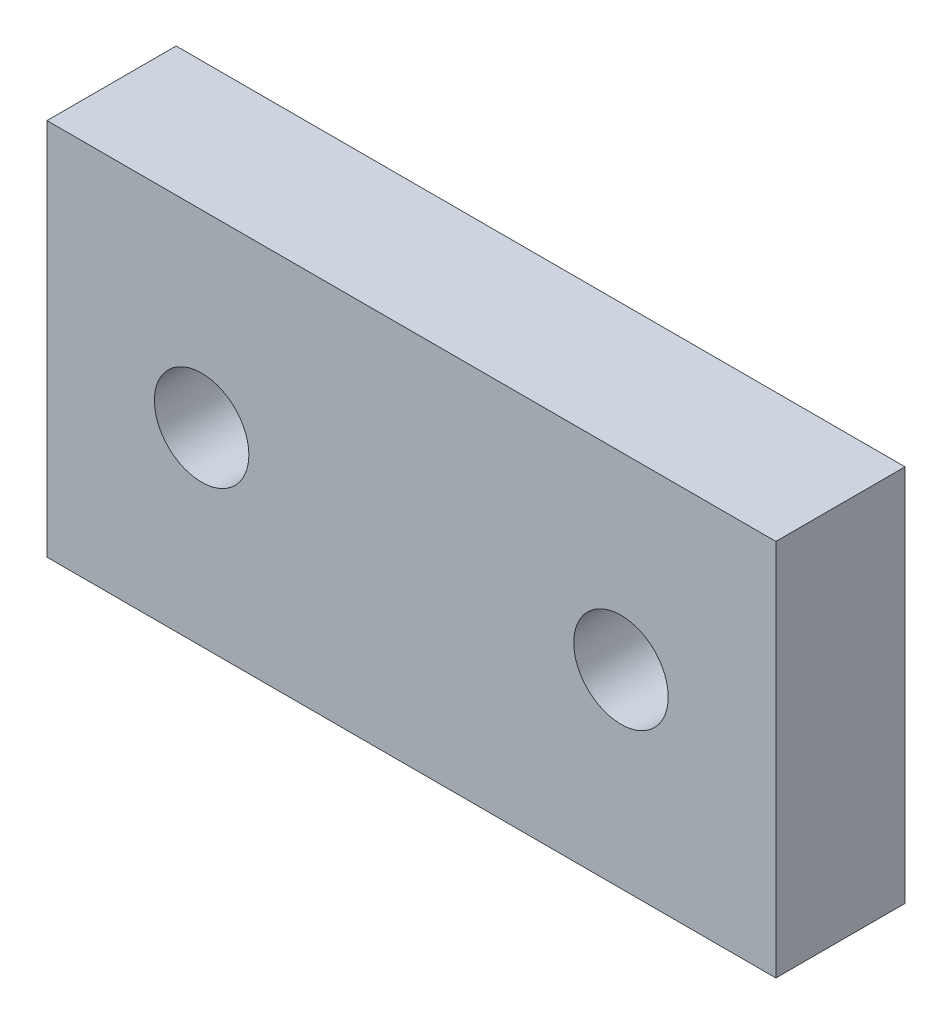
SolidWorks part; units mm, degrees
ref_plane "Front" through (0, 0, 0) normal (0, 0, 1) x (1, 0, 0)
ref_plane "Top" through (0, 0, 0) normal (0, 1, 0) x (1, 0, 0)
ref_plane "Right" through (0, 0, 0) normal (1, 0, 0) x (0, 0, -1)
sketch "Sketch1" plane through (0, 0, 0) normal (0, 0, 1) x (1, 0, 0)
  line L1 (0, 0) -> (21.2113, 0)
  line L2 (0, 0) -> (0, 11.0031)
  line L3 (0, 11.0031) -> (21.2113, 11.0031)
  line L4 (21.2113, 0) -> (21.2113, 11.0031)
  dimension "D1" = 11.0031
  dimension "D2" = 21.2113
extrude "bracketBase" add sketch "Sketch1" along normal blind 3.7588
sketch "Sketch2" plane through (0, 0, 3.7588) normal (0, 0, 1) x (1, 0, 0)
  line L1 (0, 0) -> (21.2113, 0) construction
  line L3 (0, 11.0031) -> (0, 0) construction
  circle A0 centre (4.5006, 5.5148) radius 1.375
  circle A1 centre (16.7032, 5.5148) radius 1.375
  dimension "D1" = 2.75
  dimension "D2" = 5.5148
  dimension "D3" = 4.5006
  dimension "D4" = 12.2026
extrude "Cut-Extrude1" cut sketch "Sketch2" against normal through all
